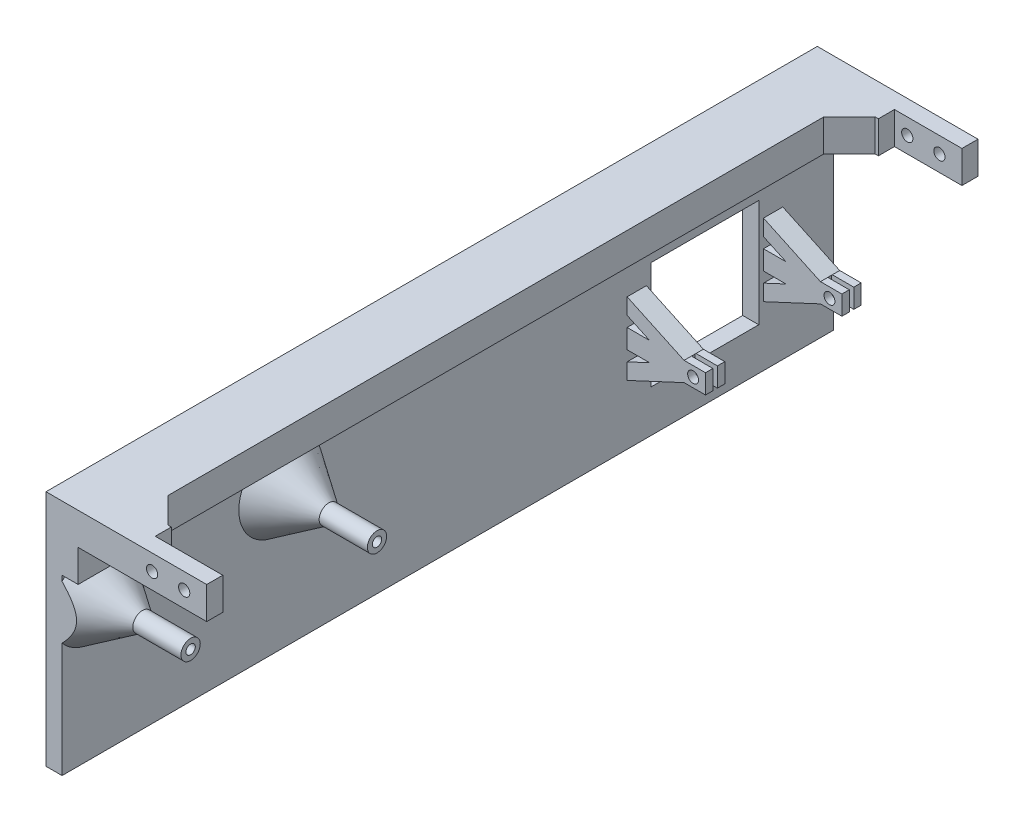
SolidWorks part; units mm, degrees
ref_plane "Front Plane" through (0, 0, 0) normal (0, 0, 1) x (1, 0, 0)
ref_plane "Top Plane" through (0, 0, 0) normal (0, 1, 0) x (1, 0, 0)
ref_plane "Right Plane" through (0, 0, 0) normal (1, 0, 0) x (0, 0, -1)
sketch "Sketch1" plane through (0, 0, 0) normal (0, 0, 1) x (1, 0, 0)
  line L0 (-10, 0) -> (0, 0)
  line L1 (0, 0) -> (0, 10)
  line L2 (0, 10) -> (10, 10)
  line L3 (10, 10) -> (10, 20)
  line L4 (10, 20) -> (-10, 20)
  line L5 (-10, 20) -> (-10, 0)
  dimension "D1" = 10
  dimension "D2" = 20
extrude "Boss-Extrude1" add sketch "Sketch1" along normal blind 240
sketch "Sketch4" plane through (0, 20, 0) normal (0, 1, 0) x (1, 0, 0)
  line L0 (10, 0) -> (40, 0)
  line L1 (40, 0) -> (40, -10)
  line L3 (10, -240) -> (10, 0) construction
  line L8 (10, -18) -> (10, 0)
  line L9 (40, -10) -> (18, -10)
  line L10 (18, -10) -> (10, -18)
  dimension "D1" = 10
  dimension "D2" = 22
  dimension "D3" = 45
  dimension "D4" = 30
extrude "Boss-Extrude3" add sketch "Sketch4" against normal up to surface (10 mm away) up to face at (5, 10, 120)
sketch "Sketch5" plane through (0, 0, 0) normal (0, 0, -1) x (-1, 0, 0)
  line L1 (-40, 10) -> (-40, 20) construction
  circle A0 centre (-33, 15) radius 1.75
  circle A1 centre (-23, 15) radius 1.75
  point P4 (-40, 15)
  dimension "D1" = 3.5
  dimension "D2" = 7
  dimension "D3" = 10
extrude "Cut-Extrude1" cut sketch "Sketch5" against normal through all
sketch "Sketch6" plane through (40, 0, 0) normal (1, 0, 0) x (0, 0, -1)
  line L5 (0, 10) -> (0, 20) construction
  line L6 (-12, 21) -> (-5, 21)
  line L7 (-12, 21) -> (-12, 9)
  line L8 (-12, 9) -> (-5, 9)
  line L9 (-5, 21) -> (-5, 9)
  point P6 (0, 15)
  point P7 (-5, 15)
  dimension "D1" = 7
  dimension "D2" = 12
  dimension "D3" = 5
extrude "Cut-Extrude2" cut sketch "Sketch6" against normal blind 21
ref_plane "Plane1" through (0, 0, 120) normal (0, 0, -1) x (-1, 0, 0)
mirror "Mirror1" about plane through (0, 0, 120) normal (0, 0, -1) of "Cut-Extrude1", "Boss-Extrude3", "Cut-Extrude2"
sketch "Sketch7" plane through (0, 0, 0) normal (0, -1, 0) x (1, 0, 0)
  line L0 (-10, 0) -> (0, 0) construction
  line L1 (-10, 240) -> (-5, 240)
  line L2 (-10, 240) -> (-10, 0)
  line L3 (-10, 0) -> (-5, 0)
  line L4 (-5, 240) -> (-5, 0)
extrude "Boss-Extrude4" add sketch "Sketch7" along normal blind 54
sketch "Sketch8" plane through (-5, 0, 0) normal (1, 0, 0) x (0, 0, -1)
  line L1 (-15.75, -21.15) -> (-21.75, -21.15)
  line L2 (-15.75, -21.15) -> (-15.75, -27.15)
  line L3 (-15.75, -27.15) -> (-21.75, -27.15)
  line L4 (-21.75, -21.15) -> (-21.75, -27.15)
  line L5 (-240, 0) -> (0, 0) construction
  line L7 (0, -54) -> (0, 0) construction
  line L9 (-64.18, -21.15) -> (-58.18, -21.15)
  line L10 (-64.18, -21.15) -> (-64.18, -27.15)
  line L11 (-64.18, -27.15) -> (-58.18, -27.15)
  line L12 (-58.18, -21.15) -> (-58.18, -27.15)
  point P4 (-18.75, -21.15)
  point P15 (-61.18, -27.15)
  point P16 (-18.75, -27.15)
  dimension "D1" = 18.75
  dimension "D2" = 21.15
  dimension "D3" = 6
  dimension "D4" = 42.43
extrude "Boss-Extrude5" add sketch "Sketch8" along normal blind 24.4
sketch "Sketch9" plane through (0, 0, 21.75) normal (0, 0, 1) x (1, 0, 0)
  line L2 (-5, -54) -> (-5, 0) construction
  line L3 (19.4, -21.15) -> (-5, -21.15) construction
  circle A0 centre (15.53, -24.25) radius 1.7
  dimension "D1" = 3.4
  dimension "D3" = 3.1
  dimension "D2" = 20.53
extrude "Cut-Extrude3" cut sketch "Sketch9" against normal through all both and the other way through all
sketch "Sketch10" plane through (19.4, 0, 0) normal (1, 0, 0) x (0, 0, -1)
  line L0 (-15.75, -21.15) -> (-21.75, -21.15) construction
  line L1 (-19.45, -21.15) -> (-18.05, -21.15)
  line L2 (-19.45, -21.15) -> (-19.45, -27.15)
  line L3 (-19.45, -27.15) -> (-18.05, -27.15)
  line L4 (-18.05, -21.15) -> (-18.05, -27.15)
  line L5 (-21.75, -27.15) -> (-15.75, -27.15) construction
  line L6 (-15.75, -21.15) -> (-21.75, -21.15) construction
  line L7 (-58.18, -21.15) -> (-64.18, -21.15) construction
  line L8 (-61.88, -21.15) -> (-60.48, -21.15)
  line L9 (-61.88, -21.15) -> (-61.88, -27.15)
  line L10 (-61.88, -27.15) -> (-60.48, -27.15)
  line L11 (-60.48, -21.15) -> (-60.48, -27.15)
  line L12 (-58.18, -21.15) -> (-64.18, -21.15) construction
  line L13 (-64.18, -27.15) -> (-58.18, -27.15) construction
  point P10 (-18.75, -21.15)
  point P11 (-18.75, -21.15)
  point P20 (-61.18, -21.15)
  point P21 (-61.18, -21.15)
  dimension "D1" = 1.4
  dimension "D2" = 1.4
extrude "Cut-Extrude4" cut sketch "Sketch10" against normal blind 7
sketch "Sketch11" plane through (0, 0, 64.18) normal (0, 0, 1) x (1, 0, 0)
  line L0 (12.7225, -21.15) -> (-5, -12.8858)
  line L1 (19.4, -21.15) -> (-5, -21.15) construction
  line L2 (-5, -54) -> (-5, 0) construction
  line L3 (-5, -12.8858) -> (-5, -17.8858)
  line L4 (-5, -17.8858) -> (2, -21.15)
  line L5 (2, -21.15) -> (12.7225, -21.15)
  line L6 (19.4, -24.15) -> (-5, -24.15) construction
  line L12 (19.4, -21.15) -> (19.4, -27.15) construction
  line L13 (-5, -30.4142) -> (2, -27.15)
  line L14 (-5, -35.4142) -> (-5, -30.4142)
  line L15 (12.7225, -27.15) -> (-5, -35.4142)
  line L16 (2, -27.15) -> (12.7225, -27.15)
  dimension "D1" = 5
  dimension "D2" = 65
  dimension "D3" = 7
extrude "Boss-Extrude6" add sketch "Sketch11" against normal up to surface (6 mm away) up to face at (17.23, -24.25, 58.18)
sketch "Sketch12" plane through (0, 0, 15.75) normal (0, 0, -1) x (-1, 0, 0)
  line L13 (-12.7225, -21.15) -> (-2, -21.15)
  line L14 (-2, -27.15) -> (-12.7225, -27.15)
  line L63 (5, -27.15) -> (5, -21.15)
  line L64 (5, -21.15) -> (-2, -21.15)
  line L65 (-2, -21.15) -> (5, -17.8858)
  line L66 (5, -17.8858) -> (5, -12.8858)
  line L67 (5, -12.8858) -> (-12.7225, -21.15)
  line L68 (-12.7225, -21.15) -> (-19.4, -21.15)
  line L69 (-19.4, -21.15) -> (-19.4, -27.15)
  line L70 (-19.4, -27.15) -> (-12.7225, -27.15)
  line L72 (-12.7225, -27.15) -> (5, -35.4142)
  line L73 (-12.7225, -27.15) -> (5, -35.4142)
  line L74 (5, -35.4142) -> (5, -30.4142)
  line L77 (-2, -21.15) -> (5, -17.8858)
  line L78 (5, -17.8858) -> (5, -12.8858)
  line L79 (5, -12.8858) -> (-12.7225, -21.15)
  line L87 (5, -35.4142) -> (5, -30.4142)
  line L88 (5, -30.4142) -> (-2, -27.15)
  line L89 (5, -30.4142) -> (-2, -27.15)
  line L90 (-2, -27.15) -> (5, -27.15)
  dimension "D1" = 0
extrude "Boss-Extrude7" add sketch "Sketch12" against normal up to surface (6 mm away) up to face at (15.53, -22.55, 21.75)
sketch "Sketch13" plane through (-5, 0, 0) normal (1, 0, 0) x (0, 0, -1)
  line L0 (-240, -54) -> (-240, 0) construction
  line L1 (0, 0) -> (-240, 0) construction
  circle A0 centre (-230, -10) radius 3
  circle A1 centre (-172, -10) radius 3
  dimension "D1" = 10
  dimension "D4" = 6
  dimension "D2" = 58
  dimension "D3" = 10
extrude "Boss-Extrude8" add sketch "Sketch13" along normal blind 30
sketch "Sketch15" plane through (25, 0, 0) normal (1, 0, 0) x (0, 0, -1)
  circle A0 centre (-230, -10) radius 1.45
  circle A1 centre (-172, -10) radius 1.45
  dimension "D1" = 2.9
extrude "Cut-Extrude5" cut sketch "Sketch15" against normal blind 5
sketch "Sketch16" plane through (-5, 0, 0) normal (1, 0, 0) x (0, 0, -1)
  line L0 (-58.18, -24.15) -> (-21.75, -24.15) construction
  line L1 (-58.18, -27.15) -> (-58.18, -21.15) construction
  line L2 (-21.75, -21.15) -> (-21.75, -27.15) construction
  line L4 (-23.215, -40.9) -> (-56.715, -40.9)
  line L5 (-23.215, -40.9) -> (-23.215, -7.4)
  line L6 (-23.215, -7.4) -> (-56.715, -7.4)
  line L7 (-56.715, -40.9) -> (-56.715, -7.4)
  line L8 (-23.215, -40.9) -> (-56.715, -7.4) construction
  line L9 (-23.215, -7.4) -> (-56.715, -40.9) construction
  point P0 (-39.965, -24.15)
  dimension "D1" = 33.5
extrude "Cut-Extrude6" cut sketch "Sketch16" against normal up to surface (5 mm away) up to face at (-10, -17, 120)
sketch "Sketch17" plane through (-5, 0, 0) normal (1, 0, 0) x (0, 0, -1)
  line L0 (0, -54) -> (-240, -54) construction
  line L1 (-129, -54) -> (-111, -54)
  line L2 (-129, -54) -> (-129, -44)
  line L3 (-129, -44) -> (-111, -44)
  line L4 (-111, -54) -> (-111, -44)
  line L5 (-240, -54) -> (-240, 0) construction
  point P8 (-120, -54)
  dimension "D1" = 10
  dimension "D2" = 18
  dimension "D3" = 120
extrude "Boss-Extrude9" [suppressed] add sketch "Sketch17" along normal blind 8.5
sketch "Sketch18" [suppressed] plane through (0, -54, 0) normal (0, -1, 0) x (1, 0, 0)
  line L0 (3.5, 129) -> (3.5, 111) construction
  line L1 (3.5, 111) -> (-5, 111) construction
  line L2 (3.5, 129) -> (-5, 129) construction
  line L3 (3.5, 129) -> (3.5, 111)
  line L4 (3.5, 111) -> (-5, 111)
  line L5 (3.5, 129) -> (-5, 129)
  line L6 (-5, 129) -> (-5, 111)
extrude "Boss-Extrude10" [suppressed] add sketch "Sketch18" along normal blind 9.5
chamfer "Chamfer1" distance 10 distance2 15 2 edges at (-5, -10, 175) (-5, -10, 233) first distance on face at (-5, -24.15, 39.965)
